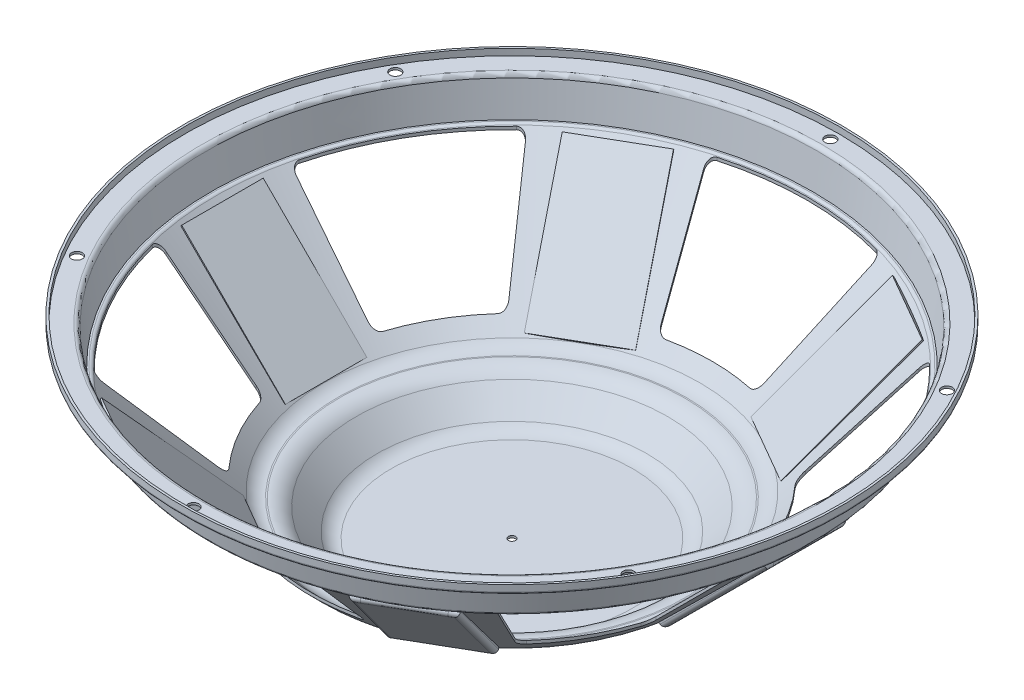
SolidWorks part; units mm, degrees
ref_plane "Спереди" through (0, 0, 0) normal (0, 0, 1) x (1, 0, 0)
ref_plane "Сверху" through (0, 0, 0) normal (0, 1, 0) x (1, 0, 0)
ref_plane "Справа" through (0, 0, 0) normal (1, 0, 0) x (0, 0, -1)
sketch "Эскиз1" plane through (0, 0, 0) normal (0, 0, 1) x (1, 0, 0)
  line L0 (1.6544, 0) -> (55.7403, 0)
  line L1 (152, 90) -> (152, 87)
  line L2 (151, 86) -> (142.8647, 86)
  line L3 (141.8751, 85.1444) -> (139.6701, 70.0338)
  line L4 (139.5453, 69.1782) -> (142, 86)
  line L5 (138.6806, 69.1782) -> (137.9595, 69.1782)
  line L6 (80.3701, 16.1451) -> (79.772, 16.1451)
  line L7 (137.2524, 68.8853) -> (87.4412, 19.0741)
  line L8 (0, 0) -> (0, 206.3191) construction
  line L9 (0, 206.3191) -> (0, -52.5162) construction
  line L10 (72.561, 13.0735) -> (62.9513, 3.0717)
  arc A0 (87.4412, 19.0741) -> (80.3701, 16.1451) centre (80.3701, 26.1451) cw
  arc A1 (79.772, 16.1451) -> (72.561, 13.0735) centre (79.772, 6.1451) ccw
  arc A2 (55.7403, 0) -> (62.9513, 3.0717) centre (55.7403, 10) ccw
  arc A3 (139.6701, 70.0338) -> (138.6806, 69.1782) centre (138.6806, 70.1782) cw
  arc A4 (137.9595, 69.1782) -> (137.2524, 68.8853) centre (137.9595, 68.1782) ccw
  arc A5 (152, 87) -> (151, 86) centre (151, 87) cw
  arc A6 (142.8647, 86) -> (141.8751, 85.1444) centre (142.8647, 85) ccw
  point P3 (152, 90)
  point P15 (84.5123, 16.1451)
  point P18 (75.5123, 16.1451)
  point P21 (60, 0)
  point P27 (137.5453, 69.1782)
  point P30 (152, 86)
  point P34 (0.2372, 0)
  dimension "D10" = 10
  dimension "D11" = 1
  dimension "D12" = 1
  dimension "D1" = 60
  dimension "D2" = 90
  dimension "D3" = 152
  dimension "D4" = 4
  dimension "D5" = 10
  dimension "D6" = 17
  dimension "D7" = 2
  dimension "D8" = 9
  dimension "D9" = 75
revolve "Повернуть-Тонкостенный6" add sketch "Эскиз1" angle 360 about L8
sketch "Эскиз4" plane through (0, 0, 0) normal (0, 1, 0) x (1, 0, 0)
  line L0 (0, 0) -> (136.154, 206.0694) construction
  line L1 (136.154, 206.0694) -> (-148.3305, -224.4985) construction
  line L2 (0, 0) -> (0, -196.0692) construction
  line L3 (0, 0) -> (144.3501, -218.4742) construction
  line L4 (144.3501, -218.4742) -> (-124.9256, 189.0752) construction
  line L5 (-22.5, -34.0538) -> (-22.5, -201.5185) construction
  line L6 (22.5, -34.0538) -> (22.5, -134.3818) construction
  line L7 (40, -60.5401) -> (40, -201.5185) construction
  line L8 (-40, -60.5401) -> (-40, -201.5185) construction
  line L10 (0, -137.2524) -> (0, -136.2524)
  line L11 (-38.6582, -127.1366) -> (-23.8228, -92.729)
  line L12 (23.8228, -92.729) -> (38.6582, -127.1366)
  circle A0 centre (0, 0) radius 72.561 construction
  arc A1 (19.3139, -90.4011) -> (23.8228, -92.729) centre (20.1496, -94.3128) cw
  circle A2 centre (0, 0) radius 137.2524 construction
  arc A3 (0, -92.4412) -> (19.3139, -90.4011) centre (0, 0) ccw
  arc A4 (0, -92.4412) -> (-19.3139, -90.4011) centre (0, 0) cw
  arc A5 (0, -136.2524) -> (36.7117, -131.2135) centre (0, 0) ccw
  arc A6 (0, -136.2524) -> (-36.7117, -131.2135) centre (0, 0) cw
  arc A7 (-19.3139, -90.4011) -> (-23.8228, -92.729) centre (-20.1496, -94.3128) ccw
  arc A8 (36.7117, -131.2135) -> (38.6582, -127.1366) centre (35.9033, -128.3244) ccw
  arc A9 (-36.7117, -131.2135) -> (-38.6582, -127.1366) centre (-35.9033, -128.3244) cw
  point P20 (22.5, -89.6612)
  point P31 (-22.5, -89.6612)
  point P34 (40, -130.2487)
  point P37 (-40, -130.2487)
  dimension "D5" = 4
  dimension "D7" = 3
  dimension "D1" = 22.5
  dimension "D2" = 22.5
  dimension "D3" = 40
  dimension "D4" = 40
  dimension "D6" = 1
extrude "Вырез-Вытянуть2" cut sketch "Эскиз4" along normal blind 108 and the other way blind 5 contours A6 A9 L11 A7 A4 A3 A1 L12 A8 A5
pattern_circular "Круговой массив2" count 6 over 360 about axis through (0, 0, 0) along (0, 1, 0) of "Вырез-Вытянуть2"
ref_plane "Плоскость2" through (32.2049, -32.2825, 0) normal (0.7063, -0.708, 0) x (-0.708, -0.7063, 0)
sketch "Эскиз9" plane through (32.2049, -32.2825, 0) normal (0.7063, -0.708, 0) x (-0.708, -0.7063, 0)
  line L3 (-143.0761, -18.7883) -> (-75.5581, -18.7883)
  line L4 (-143.0761, -18.7883) -> (-143.0761, 18.7883)
  line L5 (-143.0761, 18.7883) -> (-75.5581, 18.7883)
  line L6 (-75.5581, -18.7883) -> (-75.5581, 18.7883)
  line L7 (-109.3171, 0) -> (-109.015, 0.1681) construction
  line L8 (-109.3171, 0) -> (-108.3494, -0.5386) construction
  line L9 (-108.3494, -0.5386) -> (-109.0847, 0.2421) construction
  line L10 (-109.0847, 0.2421) -> (-109.3171, 0) construction
  point P4 (-109.3171, 0)
extrude "Бобышка-Вытянуть1" add sketch "Эскиз9" along normal blind 4
fillet "Скругление22" radius 2 4 edges at (112.4217, 42.0916, 18.7883) (136.3215, 65.9341, 0) (112.4217, 42.0916, -18.7883) (88.5218, 18.2491, 0)
pattern_circular "Круговой массив33" count 6 over 360 about axis through (0, 0, 0) along (0, 1, 0) of "Бобышка-Вытянуть1", "Скругление22"
sketch "Эскиз12" plane through (0, 0, 0) normal (0, 0, 1) x (1, 0, 0)
  line L0 (0, 0) -> (0, 125.6356) construction
  line L1 (0, 125.6356) -> (0, -28.2636) construction
  line L2 (0, 137.2481) -> (0, -40.9952) construction
  line L3 (0, -8.3774) -> (0, 137.2481) construction
sketch "Эскиз13" plane through (0, 0, 0) normal (0, 1, 0) x (1, 0, 0)
  line L0 (0, 0) -> (0, 201.4541) construction
  circle A0 centre (0, 146.8633) radius 2.5
  circle A1 centre (127.1874, 73.4317) radius 2.5
  circle A2 centre (127.1874, -73.4317) radius 2.5
  circle A3 centre (0, -146.8633) radius 2.5
  circle A4 centre (-127.1874, -73.4317) radius 2.5
  circle A5 centre (-127.1874, 73.4317) radius 2.5
  point P19 (0, 0)
  dimension "D2" = 5
  dimension "D1" = 6
extrude "Вырез-Вытянуть3" cut sketch "Эскиз13" along normal through all
